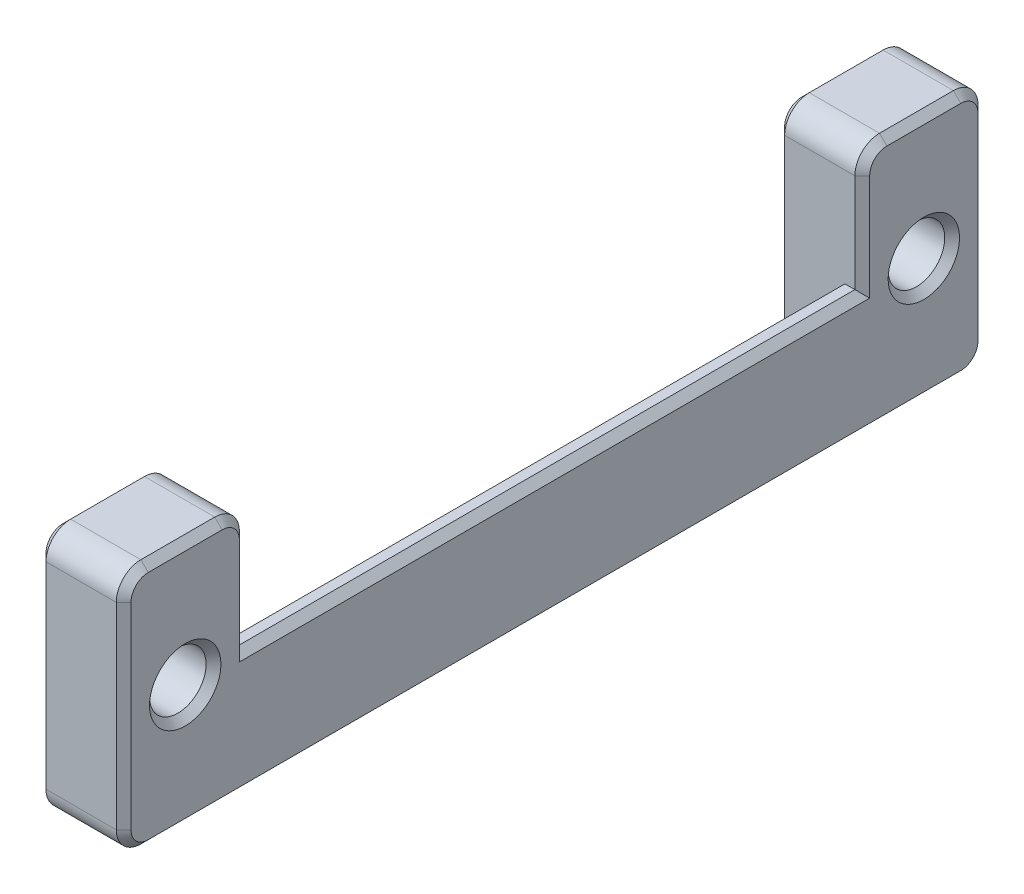
SolidWorks part; units mm, degrees
note: The reader was unsure of these and kept them because the rebuilt part matched: shared geometry of "Skizze2<2>".
ref_plane "Front" through (0, 0, 0) normal (0, 0, 1) x (1, 0, 0)
ref_plane "Top" through (0, 0, 0) normal (0, 1, 0) x (1, 0, 0)
ref_plane "Right" through (0, 0, 0) normal (1, 0, 0) x (0, 0, -1)
sketch "Skizze1" plane through (0, 0, 0) normal (0, 0, 1) x (1, 0, 0)
  line L0 (0, 0) -> (0, 10)
  line L1 (0, 0) -> (-6.9076, 0)
  line L2 (-6.9076, 0) -> (-1.4076, 10)
  line L3 (-7.25, 0) -> (-1.75, 10) construction
  line L4 (-4.0325, 10) -> (-1.75, 10) construction
  line L5 (-1.4076, 10) -> (0, 10)
  dimension "D1" = 0.3
extrude "Aufsatz-Linear austragen1" add sketch "Skizze1" along normal blind 50
sketch "Skizze2" plane through (0, 0, 50) normal (0, 0, 1) x (1, 0, 0)
  line L0 (0, 0) -> (0, 20)
  line L1 (0, 20) -> (-6.9076, 20)
  line L2 (-6.9076, 20) -> (-6.9076, 0)
  line L4 (-6.9076, 0) -> (0, 0)
extrude "Aufsatz-Linear austragen2" add sketch "Skizze2" along normal blind 10
extrude "Aufsatz-Linear austragen3" add sketch "Skizze2<2>" against normal blind 10 from surface at -50 starting at face at (-2.0788, 5, 0)
sketch "Skizze2<2>" plane through (0, 0, 50) normal (0, 0, 1) x (1, 0, 0) same geometry as "Skizze2"
chamfer "Fase1" distance 0.75 angle 45 1 edges at (-6.9076, 0, -5)
sketch "Skizze3" plane through (-6.9076, 0, 0) normal (-1, 0, 0) x (0, 0, 1)
  line L0 (-5, 20) -> (-5, 0) construction
  line L1 (-10, 20) -> (0, 20) construction
  line L2 (60, 0) -> (-10, 0) construction
  line L3 (25, 0) -> (25, 21.5206) construction
  circle A0 centre (-5, 10) radius 2.3
  circle A1 centre (55, 10) radius 2.3
  dimension "D1" = 4.6
extrude "Schnitt-Linear austragen1" cut sketch "Skizze3" against normal blind 10
fillet "Verrundung1" radius 2 6 edges at (-3.0788, 0, -10) (-3.0788, 0, 60) (-3.4538, 20, 60) (-3.4538, 20, 50) (-3.4538, 20, 0) (-3.4538, 20, -10)
chamfer "Fase2" distance 0.6 angle 45 30 edges at (0, 20, -5) (0, 19.4142, -9.4142) (0, 20, 55) (0, 19.4142, 59.4142) (0, 10, 60) (0, 0.5858, 59.4142) (0, 10, -10) (0, 0.5858, -9.4142) (0, 0, 25) (-6.9076, 9.375, 50) (-6.9076, 10, -10) (0, 10, 25) (0, 14, 0) (0, 14, 50) (0, 19.4142, -0.5858) (0, 19.4142, 50.5858) (-6.9076, 1.3376, 59.8871) (-6.9076, 10, 60) (-6.9076, 19.4142, 59.4142) (-6.9076, 20, 55) (-6.9076, 19.4142, 50.5858) (-6.9076, 9.375, 0) (-6.9076, 19.4142, -0.5858) (-6.9076, 20, -5) (-6.9076, 1.3376, -9.8871) (-6.9076, 19.4142, -9.4142) (0, 10, 57.3) (-6.9076, 12.3, 55) (0, 10, -2.7) (-6.9076, 7.7, -5)
